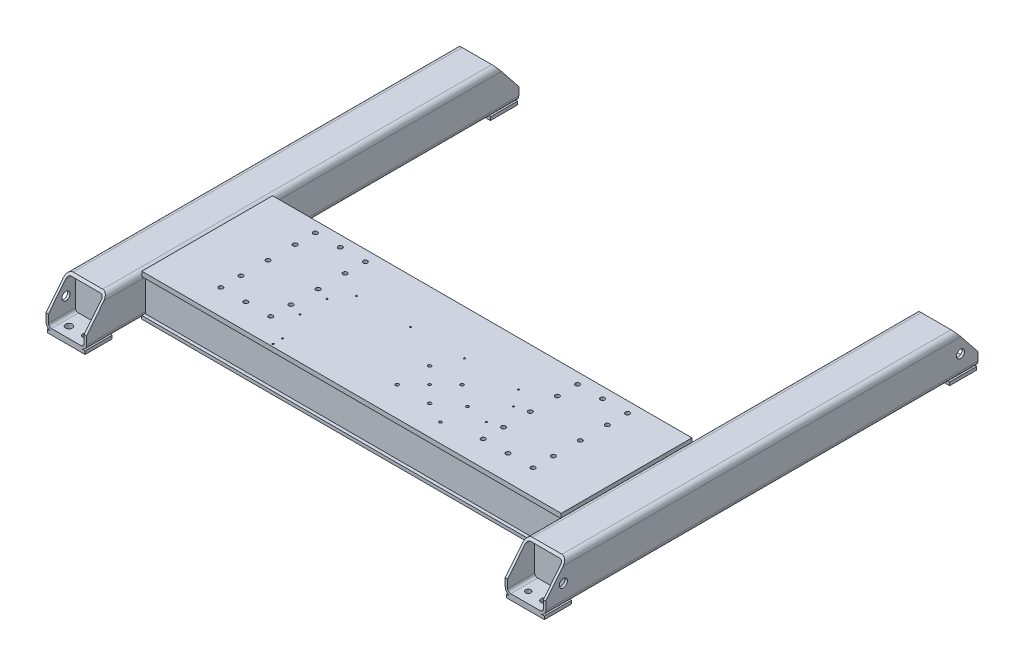
SolidWorks part; units mm, degrees
ref_plane "正面" through (0, 0, 0) normal (0, 0, 1) x (1, 0, 0)
ref_plane "平面" through (0, 0, 0) normal (0, 1, 0) x (1, 0, 0)
ref_plane "右側面" through (0, 0, 0) normal (1, 0, 0) x (0, 0, -1)
sketch "ｽｹｯﾁ1" plane through (0, 0, 0) normal (0, 0, 1) x (1, 0, 0)
  line L0 (-905, 12) -> (-795, 12)
  line L1 (-775, 32) -> (-775, 142)
  line L2 (-795, 162) -> (-905, 162)
  line L3 (-925, 142) -> (-925, 32)
  line L4 (795, 12) -> (905, 12)
  line L5 (925, 32) -> (925, 142)
  line L6 (905, 162) -> (795, 162)
  line L7 (775, 142) -> (775, 32)
  arc A0 (-795, 12) -> (-775, 32) centre (-795, 32) ccw
  arc A1 (-775, 142) -> (-795, 162) centre (-795, 142) ccw
  arc A2 (-905, 162) -> (-925, 142) centre (-905, 142) ccw
  arc A3 (-925, 32) -> (-905, 12) centre (-905, 32) ccw
  arc A4 (905, 12) -> (925, 32) centre (905, 32) ccw
  arc A5 (925, 142) -> (905, 162) centre (905, 142) ccw
  arc A6 (795, 162) -> (775, 142) centre (795, 142) ccw
  arc A7 (775, 32) -> (795, 12) centre (795, 32) ccw
extrude "ﾎﾞｽ - 押し出し1" add sketch "ｽｹｯﾁ1" against normal blind 800 and the other way blind 800
sketch "ｽｹｯﾁ2" plane through (0, 0, 0) normal (0, 0, 1) x (1, 0, 0)
  line L0 (-905, 21) -> (-795, 21)
  line L1 (-784, 32) -> (-784, 142)
  line L2 (-795, 153) -> (-905, 153)
  line L3 (-916, 142) -> (-916, 32)
  line L4 (795, 21) -> (905, 21)
  line L5 (916, 32) -> (916, 142)
  line L6 (905, 153) -> (795, 153)
  line L7 (784, 142) -> (784, 32)
  arc A0 (-795, 21) -> (-784, 32) centre (-795, 32) ccw
  arc A1 (-784, 142) -> (-795, 153) centre (-795, 142) ccw
  arc A2 (-905, 153) -> (-916, 142) centre (-905, 142) ccw
  arc A3 (-916, 32) -> (-905, 21) centre (-905, 32) ccw
  arc A4 (905, 21) -> (916, 32) centre (905, 32) ccw
  arc A5 (916, 142) -> (905, 153) centre (905, 142) ccw
  arc A6 (795, 153) -> (784, 142) centre (795, 142) ccw
  arc A7 (784, 32) -> (795, 21) centre (795, 32) ccw
extrude "ｶｯﾄ - 押し出し1" cut sketch "ｽｹｯﾁ2" against normal through all and the other way through all
sketch "ｽｹｯﾁ3" plane through (0, 0, 0) normal (1, 0, 0) x (0, 0, -1)
  line L0 (-582, 24) -> (-570, 24)
  line L1 (-570, 24) -> (-570, 149)
  line L2 (-570, 149) -> (-582, 149)
  line L3 (-582, 149) -> (-582, 24)
  line L4 (-134, 24) -> (-122, 24)
  line L5 (-122, 24) -> (-122, 149)
  line L6 (-122, 149) -> (-134, 149)
  line L7 (-134, 149) -> (-134, 24)
extrude "ﾎﾞｽ - 押し出し2" add sketch "ｽｹｯﾁ3" against normal blind 775 and the other way blind 775
sketch "ｽｹｯﾁ4" plane through (0, 0, 0) normal (1, 0, 0) x (0, 0, -1)
  line L0 (-570, 24) -> (-134, 24)
  line L1 (-134, 24) -> (-134, 149)
  line L2 (-134, 149) -> (-570, 149)
  line L3 (-570, 149) -> (-570, 24)
extrude "ﾎﾞｽ - 押し出し3" add sketch "ｽｹｯﾁ4" against normal blind 6 and the other way blind 6
sketch "ｽｹｯﾁ5" plane through (0, 0, 0) normal (1, 0, 0) x (0, 0, -1)
  line L0 (-594, 12) -> (-110, 12)
  line L1 (-110, 12) -> (-110, 24)
  line L2 (-110, 24) -> (-594, 24)
  line L3 (-594, 24) -> (-594, 12)
sketch "ｽｹｯﾁ6" plane through (0, 0, 0) normal (1, 0, 0) x (0, 0, -1)
  line L0 (-594, 12) -> (-110, 12)
  line L1 (-110, 12) -> (-110, 24)
  line L2 (-110, 24) -> (-594, 24)
  line L3 (-594, 24) -> (-594, 12)
extrude "ﾎﾞｽ - 押し出し5" add sketch "ｽｹｯﾁ6" against normal blind 776.6497 and the other way blind 776.6497
sketch "ｽｹｯﾁ7" plane through (0, 0, 0) normal (1, 0, 0) x (0, 0, -1)
  line L0 (-594, 149) -> (-110, 149)
  line L1 (-110, 149) -> (-110, 166)
  line L2 (-110, 166) -> (-594, 166)
  line L3 (-594, 166) -> (-594, 149)
extrude "ﾎﾞｽ - 押し出し6" add sketch "ｽｹｯﾁ7" against normal blind 776.245 and the other way blind 776.245
sketch "ｽｹｯﾁ8" plane through (0, 0, 0) normal (0, 1, 0) x (1, 0, 0)
  line L0 (-920, -800) -> (-780, -800)
  line L1 (-780, -800) -> (-780, -700)
  line L2 (-780, -700) -> (-920, -700)
  line L3 (-920, -700) -> (-920, -800)
  line L4 (-920, 700) -> (-780, 700)
  line L5 (-780, 700) -> (-780, 800)
  line L6 (-780, 800) -> (-920, 800)
  line L7 (-920, 800) -> (-920, 700)
  line L8 (780, -800) -> (920, -800)
  line L9 (920, -800) -> (920, -700)
  line L10 (920, -700) -> (780, -700)
  line L11 (780, -700) -> (780, -800)
  line L12 (780, 700) -> (920, 700)
  line L13 (920, 700) -> (920, 800)
  line L14 (920, 800) -> (780, 800)
  line L15 (780, 800) -> (780, 700)
extrude "ﾎﾞｽ - 押し出し7" add sketch "ｽｹｯﾁ8" along normal blind 12
ref_plane "平面1" through (0, 0, 700) normal (0, 0, 1) x (1, 0, 0)
ref_plane "平面2" through (0, 0, -700) normal (0, 0, 1) x (1, 0, 0)
sketch "ｽｹｯﾁ11" plane through (0, 0, 700) normal (0, 0, 1) x (1, 0, 0)
  line L0 (-916.5, 20.5) -> (-783.5, 20.5)
  line L1 (-783.5, 20.5) -> (-783.5, 153.5)
  line L2 (-783.5, 153.5) -> (-916.5, 153.5)
  line L3 (-916.5, 153.5) -> (-916.5, 20.5)
  line L4 (783.5, 20.5) -> (916.5, 20.5)
  line L5 (916.5, 20.5) -> (916.5, 153.5)
  line L6 (916.5, 153.5) -> (783.5, 153.5)
  line L7 (783.5, 153.5) -> (783.5, 20.5)
extrude "ﾎﾞｽ - 押し出し8" add sketch "ｽｹｯﾁ11" against normal blind 9
sketch "ｽｹｯﾁ12" plane through (0, 0, -700) normal (0, 0, 1) x (1, 0, 0)
  line L0 (-916.5, 20.5) -> (-783.5, 20.5)
  line L1 (-783.5, 20.5) -> (-783.5, 153.5)
  line L2 (-783.5, 153.5) -> (-916.5, 153.5)
  line L3 (-916.5, 153.5) -> (-916.5, 20.5)
  line L4 (783.5, 20.5) -> (916.5, 20.5)
  line L5 (916.5, 20.5) -> (916.5, 153.5)
  line L6 (916.5, 153.5) -> (783.5, 153.5)
  line L7 (783.5, 153.5) -> (783.5, 20.5)
extrude "ﾎﾞｽ - 押し出し9" add sketch "ｽｹｯﾁ12" along normal blind 9
sketch "ｽｹｯﾁ13" plane through (0, 0, 0) normal (1, 0, 0) x (0, 0, -1)
  line L0 (-850, -0.5) -> (-700, 187)
  line L1 (-700, 187) -> (-700, 260)
  line L2 (-700, 260) -> (-850, 260)
  line L3 (-850, 260) -> (-850, -0.5)
extrude "ｶｯﾄ - 押し出し2" cut sketch "ｽｹｯﾁ13" against normal through all and the other way through all
sketch "ｽｹｯﾁ14" plane through (0, 0, 0) normal (1, 0, 0) x (0, 0, -1)
  line L0 (850, -0.5) -> (700, 187)
  line L1 (700, 187) -> (700, 260)
  line L2 (700, 260) -> (850, 260)
  line L3 (850, 260) -> (850, -0.5)
extrude "ｶｯﾄ - 押し出し3" cut sketch "ｽｹｯﾁ14" against normal through all and the other way through all
ref_plane "平面3" through (0, 166, 0) normal (0, 1, 0) x (1, 0, 0)
sketch "ｽｹｯﾁ16" plane through (0, 166, 0) normal (0, 1, 0) x (1, 0, 0)
  circle A0 centre (-578, -500) radius 8
  circle A1 centre (-485.5, -500) radius 8
  circle A2 centre (-393, -500) radius 8
  circle A3 centre (393, -500) radius 8
  circle A4 centre (485.5, -500) radius 8
  circle A5 centre (578, -500) radius 8
  circle A6 centre (-578, -425) radius 8
  circle A7 centre (-393, -425) radius 8
  circle A8 centre (393, -425) radius 8
  circle A9 centre (578, -425) radius 8
  circle A10 centre (-578, -225) radius 8
  circle A11 centre (-393, -225) radius 8
  circle A12 centre (393, -225) radius 8
  circle A13 centre (578, -225) radius 8
  circle A14 centre (-578, -150) radius 8
  circle A15 centre (-485.5, -150) radius 8
  circle A16 centre (-393, -150) radius 8
  circle A17 centre (393, -150) radius 8
  circle A18 centre (485.5, -150) radius 8
  circle A19 centre (578, -150) radius 8
extrude "ｶｯﾄ - 押し出し4" cut sketch "ｽｹｯﾁ16" against normal blind 17
sketch "ｽｹｯﾁ17" plane through (0, 166, 0) normal (0, 1, 0) x (1, 0, 0)
  circle A0 centre (-578, -325) radius 8
  circle A1 centre (-393, -325) radius 8
  circle A2 centre (393, -325) radius 8
  circle A3 centre (578, -325) radius 8
extrude "ｶｯﾄ - 押し出し5" cut sketch "ｽｹｯﾁ17" against normal blind 17
sketch "ｽｹｯﾁ18" plane through (0, 166, 0) normal (0, 1, 0) x (1, 0, 0)
  circle A0 centre (-300, -276) radius 3
  circle A1 centre (-100, -276) radius 3
  circle A2 centre (100, -276) radius 3
  circle A3 centre (300, -276) radius 3
extrude "ｶｯﾄ - 押し出し6" cut sketch "ｽｹｯﾁ18" against normal blind 12
sketch "ｽｹｯﾁ19" plane through (0, 166, 0) normal (0, 1, 0) x (1, 0, 0)
  circle A0 centre (-345, -440) radius 3
  circle A1 centre (-345, -340) radius 3
  circle A2 centre (345, -440) radius 3
  circle A3 centre (345, -340) radius 3
extrude "ｶｯﾄ - 押し出し7" cut sketch "ｽｹｯﾁ19" against normal blind 17
sketch "ｽｹｯﾁ20" plane through (0, 166, 0) normal (0, 1, 0) x (1, 0, 0)
  circle A0 centre (-300, -584) radius 3
  circle A1 centre (-300, -549) radius 3
extrude "ｶｯﾄ - 押し出し8" cut sketch "ｽｹｯﾁ20" against normal blind 17
sketch "ｽｹｯﾁ21" plane through (0, 166, 0) normal (0, 1, 0) x (1, 0, 0)
  circle A0 centre (60, -485) radius 6
  circle A1 centre (180, -485) radius 6
  circle A2 centre (60, -365) radius 6
  circle A3 centre (180, -365) radius 6
extrude "ｶｯﾄ - 押し出し9" cut sketch "ｽｹｯﾁ21" against normal blind 17
sketch "ｽｹｯﾁ22" plane through (0, 166, 0) normal (0, 1, 0) x (1, 0, 0)
  circle A0 centre (120, -425) radius 5
extrude "ｶｯﾄ - 押し出し10" cut sketch "ｽｹｯﾁ22" against normal blind 17
sketch "ｽｹｯﾁ23" plane through (0, 166, 0) normal (0, 1, 0) x (1, 0, 0)
  circle A0 centre (260, -525) radius 5
  circle A1 centre (260, -425) radius 5
extrude "ｶｯﾄ - 押し出し11" cut sketch "ｽｹｯﾁ23" against normal blind 17
sketch "ｽｹｯﾁ24" plane through (0, 0, 0) normal (0, 1, 0) x (1, 0, 0)
  circle A0 centre (-880, -760) radius 12.5
  circle A1 centre (-880, 760) radius 12.5
  circle A2 centre (880, -760) radius 12.5
  circle A3 centre (880, 760) radius 12.5
sketch "ｽｹｯﾁ25" plane through (0, 0, 0) normal (0, 1, 0) x (1, 0, 0)
  circle A0 centre (-880, -760) radius 12.5
  circle A1 centre (-880, 760) radius 12.5
  circle A2 centre (880, -760) radius 12.5
  circle A3 centre (880, 760) radius 12.5
extrude "ｶｯﾄ - 押し出し13" cut sketch "ｽｹｯﾁ25" along normal blind 21
sketch "ｽｹｯﾁ26" plane through (0, 0, 0) normal (0, 1, 0) x (1, 0, 0)
  circle A0 centre (-820, -760) radius 10
  circle A1 centre (-820, 760) radius 10
  circle A2 centre (820, -760) radius 10
  circle A3 centre (820, 760) radius 10
sketch "ｽｹｯﾁ27" plane through (0, 0, 0) normal (0, 1, 0) x (1, 0, 0)
  circle A0 centre (-820, -760) radius 10
  circle A1 centre (-820, 760) radius 10
  circle A2 centre (820, -760) radius 10
  circle A3 centre (820, 760) radius 10
extrude "ｶｯﾄ - 押し出し15" cut sketch "ｽｹｯﾁ27" along normal blind 21
ref_plane "平面4" through (-925, 0, 0) normal (1, 0, 0) x (0, 0, -1)
sketch "ｽｹｯﾁ29" plane through (-925, 0, 0) normal (1, 0, 0) x (0, 0, -1)
  circle A0 centre (-735, 87) radius 15
  circle A1 centre (735, 87) radius 15
sketch "ｽｹｯﾁ30" plane through (-925, 0, 0) normal (1, 0, 0) x (0, 0, -1)
  circle A0 centre (-735, 87) radius 15
  circle A1 centre (735, 87) radius 15
extrude "ｶｯﾄ - 押し出し17" cut sketch "ｽｹｯﾁ30" along normal blind 9
ref_plane "平面5" through (925, 0, 0) normal (1, 0, 0) x (0, 0, -1)
sketch "ｽｹｯﾁ32" plane through (925, 0, 0) normal (1, 0, 0) x (0, 0, -1)
  circle A0 centre (-735, 87) radius 15
  circle A1 centre (735, 87) radius 15
extrude "ｶｯﾄ - 押し出し18" cut sketch "ｽｹｯﾁ32" against normal blind 9
